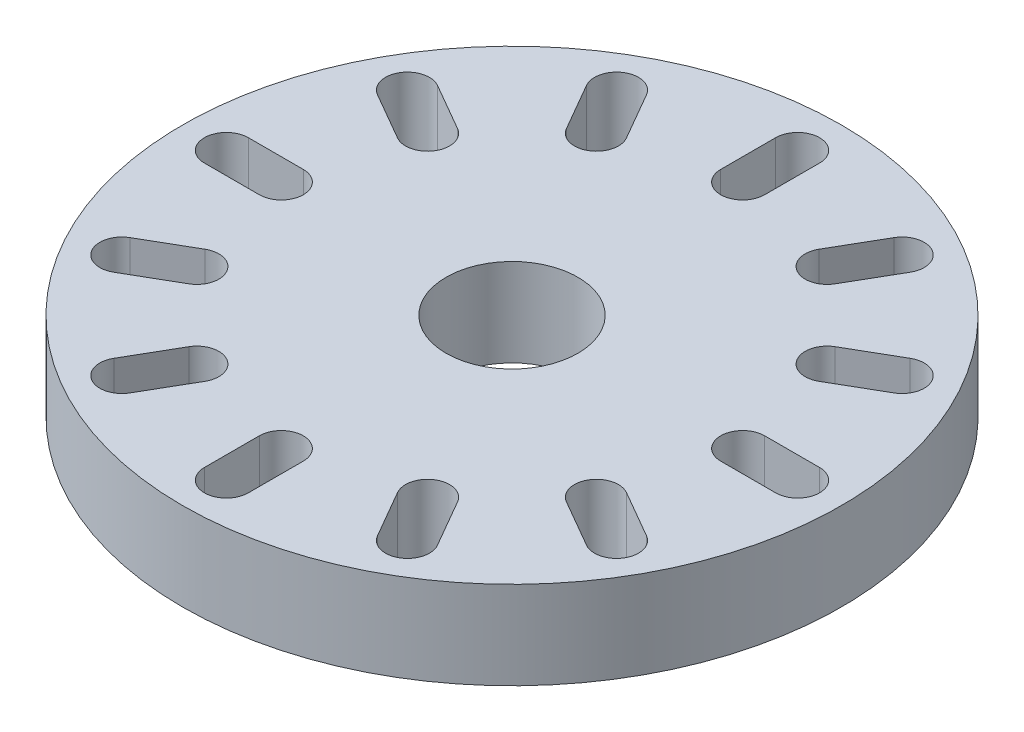
SolidWorks part; units mm, degrees
ref_plane "前视基准面" through (0, 0, 0) normal (0, 0, 1) x (1, 0, 0)
ref_plane "上视基准面" through (0, 0, 0) normal (0, 1, 0) x (1, 0, 0)
ref_plane "右视基准面" through (0, 0, 0) normal (1, 0, 0) x (0, 0, -1)
sketch "草图1" plane through (0, 0, 0) normal (0, 1, 0) x (1, 0, 0)
  circle A0 centre (0, 0) radius 30
  circle A1 centre (0, 0) radius 6
extrude "凸台-拉伸1" add sketch "草图1" along normal blind 8
sketch "草图2" plane through (0, 0, 0) normal (0, 1, 0) x (1, 0, 0)
  line L0 (21, 2) -> (26, 2)
  line L1 (26, -2) -> (21, -2)
  arc A0 (26, 2) -> (26, -2) centre (26, 0) cw
  arc A1 (21, -2) -> (21, 2) centre (21, 0) cw
extrude "切除-拉伸1" cut sketch "草图2" against normal mid plane 122
ref_axis "基准轴1" through (0, -0.4, 0) along (0, 1, 0)
pattern_circular "阵列(圆周)1" count 12 over 360 about axis through (0, -0.4, 0) along (0, 1, 0) of "切除-拉伸1"
